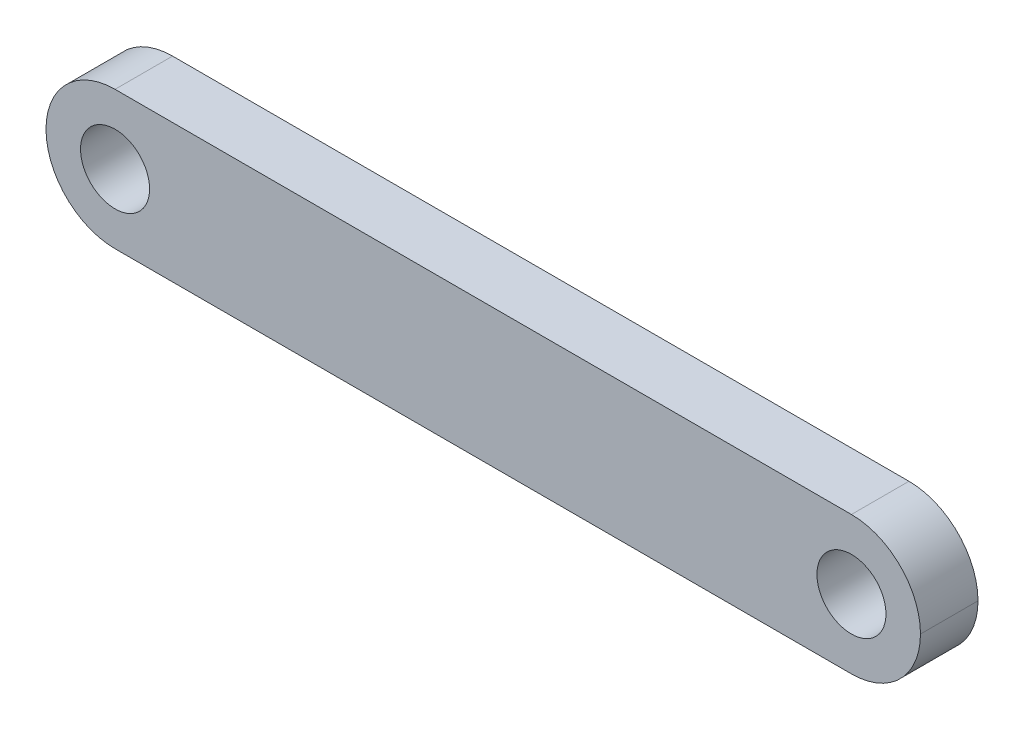
SolidWorks part; units mm, degrees
material "Messing"
ref_plane "Ebene vorne" through (0, 0, 0) normal (0, 0, 1) x (1, 0, 0)
ref_plane "Ebene oben" through (0, 0, 0) normal (0, 1, 0) x (1, 0, 0)
ref_plane "Ebene rechts" through (0, 0, 0) normal (1, 0, 0) x (0, 0, -1)
sketch "Skizze1" plane through (0, 0, 0) normal (0, 0, 1) x (1, 0, 0)
  line L1 (38, -6) -> (-38, -6)
  line L2 (38, -6) -> (38, 6)
  line L3 (38, 6) -> (-38, 6)
  line L4 (-38, -6) -> (-38, 6)
  line L5 (38, -6) -> (-38, 6) construction
  line L6 (38, 6) -> (-38, -6) construction
  point P0 (0, 0)
  dimension "D1" = 76
  dimension "D2" = 12
extrude "Aufsatz-Linear austragen1" add sketch "Skizze1" along normal blind 5
fillet "Verrundung1" radius 6 4 edges at (-38, -6, 2.5) (38, -6, 2.5) (38, 6, 2.5) (-38, 6, 2.5)
hole_wizard "Ø6.0 (6) Durchmesser Bohrung3" positions "Skizze2" profile "Skizze3" hole size "Ø6.0" standard "DIN" end condition through all
sketch "Skizze2" plane through (0, 0, 5) normal (0, 0, 1) x (1, 0, 0)
  line L0 (32, 6) -> (-32, 6) construction
  point P0 (-32, 0)
  point P2 (32, 0)
  dimension "D1" = 64
  dimension "D2" = 32
  dimension "D3" = 6
sketch "Skizze3" plane through (-32, 0, 5) normal (1, 0, 0) x (0, -1, 0)
  line L0 (0, 0) -> (0, 5)
  line L1 (0, 5) -> (3, 5)
  line L2 (3, 5) -> (3, 0)
  line L5 (3, 0) -> (0, 0)
  line L11 (0, -6.35) -> (0, 107.95) construction
  dimension "Bohrerdurchmesser" = 6
  dimension "Bohrungstiefe" = 5
